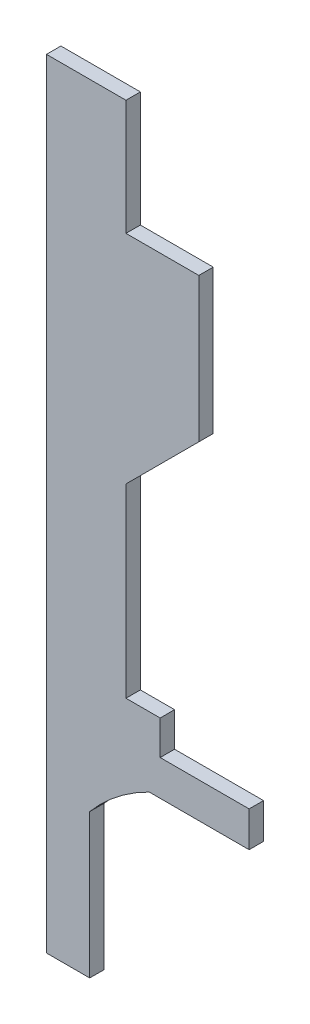
SolidWorks part; units mm, degrees
material "Balsa"
ref_plane "Plan de face" through (0, 0, 0) normal (0, 0, 1) x (1, 0, 0)
ref_plane "Plan de dessus" through (0, 0, 0) normal (0, 1, 0) x (1, 0, 0)
ref_plane "Plan de droite" through (0, 0, 0) normal (1, 0, 0) x (0, 0, -1)
sketch "Esquisse1" plane through (0, 0, 0) normal (0, 0, 1) x (1, 0, 0)
  line L0 (70.2972, 66.1864) -> (70.2972, 78.4512)
  line L1 (0, 270) -> (27.5725, 270)
  line L2 (70.2972, 78.4512) -> (39.4393, 78.4512)
  line L3 (15, 50) -> (15, 0)
  line L4 (0, 270) -> (0, 0)
  line L5 (15, 0) -> (0, 0)
  line L6 (27.5725, 270) -> (27.5725, 230)
  line L7 (35.67, 66.1864) -> (70.2972, 66.1864)
  line L8 (27.5725, 154.7175) -> (52.855, 180)
  line L9 (52.855, 180) -> (52.855, 230)
  line L10 (27.5725, 230) -> (52.855, 230)
  line L11 (27.5725, 154.7175) -> (27.5725, 90.334)
  line L12 (27.5725, 90.334) -> (39.4393, 90.334)
  line L13 (39.4393, 90.334) -> (39.4393, 78.4512)
  arc A0 (15, 50) -> (35.67, 66.1864) centre (63.603, 9.2251) cw
  dimension "D1" = 270
  dimension "D2" = 40
  dimension "D3" = 15
  dimension "D4" = 50
  dimension "D5" = 50
  dimension "D6" = 135
extrude "Boss.-Extru.1" add sketch "Esquisse1" along normal blind 5
